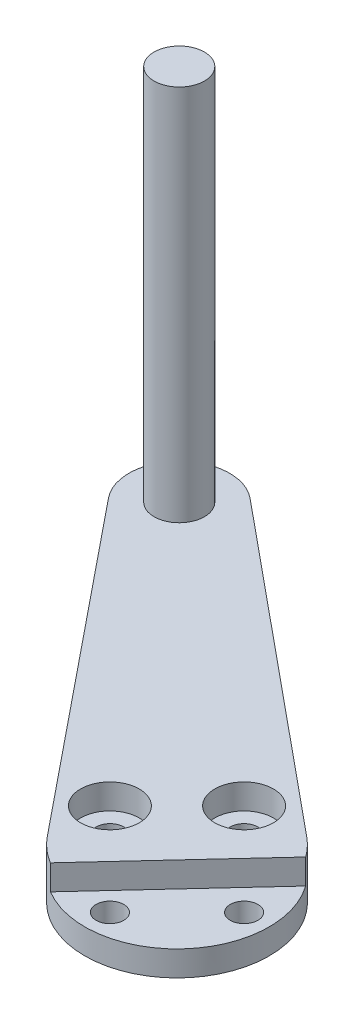
SolidWorks part; units mm, degrees
ref_plane "前视基准面" through (0, 0, 0) normal (0, 0, 1) x (1, 0, 0)
ref_plane "上视基准面" through (0, 0, 0) normal (0, 1, 0) x (1, 0, 0)
ref_plane "右视基准面" through (0, 0, 0) normal (1, 0, 0) x (0, 0, -1)
other "Configuration Table"
sketch "草图1" plane through (0, 0, 0) normal (0, 1, 0) x (1, 0, 0)
  line L0 (0, 0) -> (0, -20.9394) construction
  line L5 (-10.0425, -10.0425) -> (10.0425, 10.0425) construction
  line L6 (-10.0425, 10.0425) -> (10.0425, -10.0425) construction
  line L8 (0, 0) -> (17.825, 0) construction
  circle A4 centre (0, 0) radius 11
  circle A5 centre (0, -8) radius 1.65
  circle A6 centre (8, 0) radius 1.65
  point P0 (0, 0)
  dimension "D4" = 8
  dimension "D5" = 8
extrude "凸台-拉伸2" add sketch "草图1" along normal blind 3
sketch "草图2" plane through (0, 3, 0) normal (0, 1, 0) x (1, 0, 0)
  line L4 (8.9523, 6.3919) -> (-5.6631, -9.4303)
  circle A0 centre (0, 0) radius 11 construction
  arc A3 (8.9523, 6.3919) -> (-5.6631, -9.4303) centre (0, 0) ccw
extrude "凸台-拉伸3" add sketch "草图2" along normal blind 3
sketch "草图3" plane through (0, 6, 0) normal (0, 1, 0) x (1, 0, 0)
  line L0 (-5.6631, -9.4303) -> (8.9523, 6.3919)
  line L1 (0, 0) -> (-31.6987, 31.9404) construction
  line L2 (-39.8808, 31.7099) -> (-8.5434, -6.929)
  line L3 (-31.4061, 40.1206) -> (6.9937, 8.4905)
  arc A0 (8.9523, 6.3919) -> (6.9937, 8.4905) centre (0, 0) ccw
  arc A1 (-31.4061, 40.1206) -> (-39.8808, 31.7099) centre (-35.2208, 35.4894) ccw
  arc A3 (-8.5434, -6.929) -> (-5.6631, -9.4303) centre (0, 0) ccw
  dimension "D2" = 12
  dimension "D1" = 50
extrude "凸台-拉伸4" add sketch "草图3" against normal blind 6
sketch "草图4" plane through (0, 6, 0) normal (0, 1, 0) x (1, 0, 0)
  circle A0 centre (-35.2208, 35.4894) radius 3
extrude "凸台-拉伸5" add sketch "草图4" along normal blind 45
sketch "草图5" plane through (0, 3, 0) normal (0, 1, 0) x (1, 0, 0)
  circle A0 centre (-8, 0) radius 1.65
  circle A1 centre (0, 8) radius 1.65
  dimension "D1" = 8
  dimension "D2" = 8
extrude "凸台-拉伸6" add sketch "草图5" along normal mid plane 10 separate body
combine bodies "组合1" operation type subtract main body 149 bodies to subtract 151 150
sketch "草图6" plane through (0, 3, 0) normal (0, 1, 0) x (1, 0, 0)
  circle A0 centre (0, 8) radius 3.5
  circle A1 centre (-8, 0) radius 3.5
extrude "凸台-拉伸7" add sketch "草图6" along normal blind 4 separate body
combine bodies "组合2" operation type subtract main body 152 bodies to subtract 153 154
